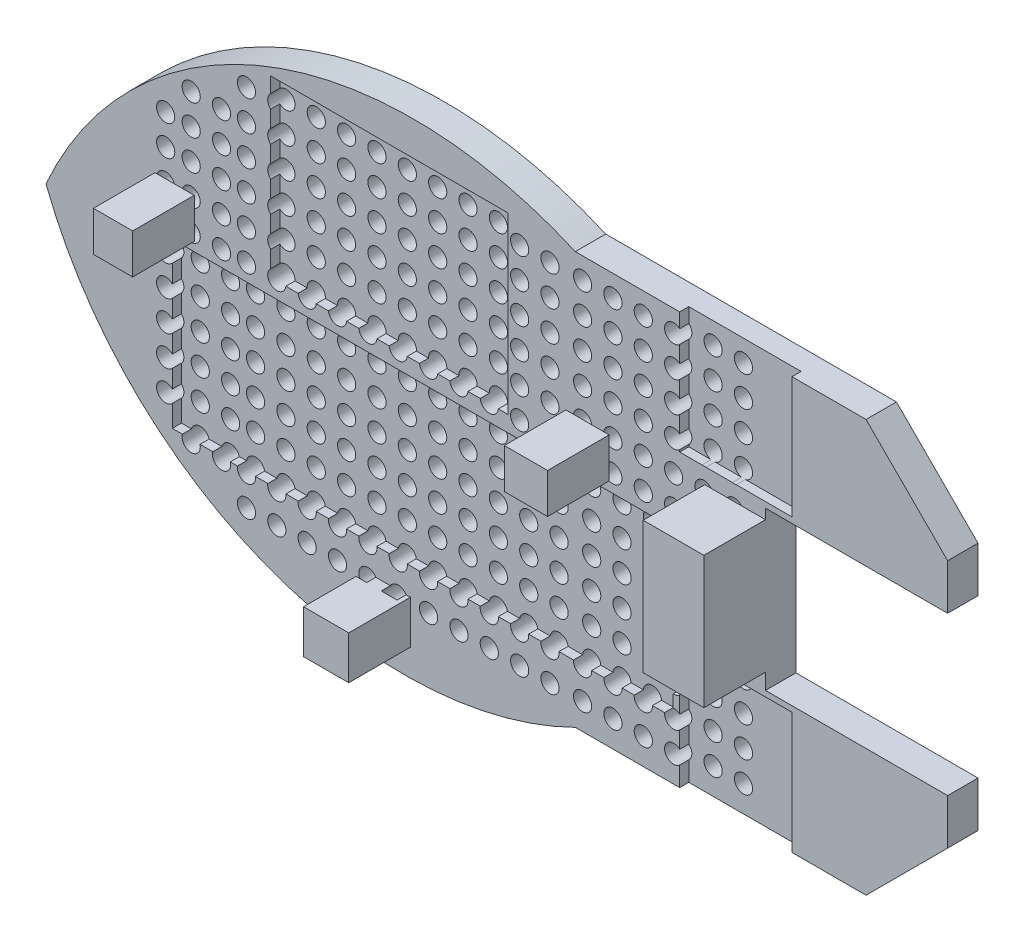
SolidWorks part; units mm, degrees
ref_plane "Front Plane" through (0, 0, 0) normal (0, 0, 1) x (1, 0, 0)
ref_plane "Top Plane" through (0, 0, 0) normal (0, 1, 0) x (1, 0, 0)
ref_plane "Right Plane" through (0, 0, 0) normal (1, 0, 0) x (0, 0, -1)
sketch "Sketch1" plane through (0, 0, 0) normal (0, 0, 1) x (1, 0, 0)
  line L0 (0, 0) -> (0, 26)
  line L1 (0, 0) -> (0, -26)
  line L2 (0, 26) -> (60, 26)
  line L3 (0, -26) -> (60, -26)
  line L4 (60, 26) -> (60, 41)
  line L5 (60, -26) -> (60, -41)
  line L6 (60, 41) -> (33.1299, 67.8701)
  line L7 (33.1299, 67.8701) -> (-62.6465, 67.8701)
  line L8 (60, -41) -> (33.1299, -67.8701)
  line L9 (33.1299, -67.8701) -> (-62.6465, -67.8701)
  line L10 (-62.6465, 67.8701) -> (-62.6465, 83.5456) construction
  line L11 (-62.6465, 83.5456) -> (-62.6465, -86.6983) construction
  arc A3 (-62.6465, 67.8701) -> (-237.0271, 0) centre (-115.9017, -53.2553) ccw
  arc A4 (-237.0271, 0) -> (-62.6465, -67.8701) centre (-118.8598, 45.6551) ccw
  point P15 (-62.6465, -67.8701)
  dimension "D1" = 26
  dimension "D2" = 26
  dimension "D3" = 60
  dimension "D4" = 15
  dimension "D5" = 15
  dimension "D6" = 135
  dimension "D7" = 38
  dimension "D8" = 38
  dimension "D9" = 135
extrude "Boss-Extrude1" add sketch "Sketch1" along normal blind 10 and the other way blind 0.01
sketch "Sketch3" plane through (0, 0, 10) normal (0, 0, 1) x (1, 0, 0)
  line L0 (33.1299, 67.8701) -> (-62.6465, 67.8701) construction
  line L1 (-28.273, 67.8701) -> (8.727, 67.8701)
  line L2 (-28.273, 67.8701) -> (-28.273, 27.8701)
  line L3 (-28.273, 27.8701) -> (8.727, 27.8701)
  line L4 (8.727, 67.8701) -> (8.727, 27.8701)
  dimension "D1" = 40
  dimension "D2" = 37
extrude "Cut-Extrude1" cut sketch "Sketch3" against normal blind 3 contours L2 L1 L4 L3
sketch "Sketch5" plane through (0, 0, 10) normal (0, 0, 1) x (1, 0, 0)
  line L0 (-62.6465, -67.8701) -> (33.1299, -67.8701) construction
  line L1 (-28.273, -27.8701) -> (8.727, -27.8701)
  line L2 (-28.273, -27.8701) -> (-28.273, -67.8701)
  line L3 (-28.273, -67.8701) -> (8.727, -67.8701)
  line L4 (8.727, -27.8701) -> (8.727, -67.8701)
extrude "Cut-Extrude3" cut sketch "Sketch5" against normal blind 3
sketch "Sketch7" plane through (0, 0, 10) normal (0, 0, 1) x (1, 0, 0)
  line L1 (-195.4131, 5.0562) -> (-30.4131, 5.0562)
  line L2 (-195.4131, 5.0562) -> (-195.4131, -48.9438)
  line L3 (-195.4131, -48.9438) -> (-30.4131, -48.9438)
  line L4 (-30.4131, 5.0562) -> (-30.4131, -48.9438)
  dimension "D1" = 54
  dimension "D2" = 165
extrude "Cut-Extrude4" cut sketch "Sketch7" against normal blind 3
sketch "Sketch8" plane through (0, 0, 10) normal (0, 0, 1) x (1, 0, 0)
  line L1 (-162.9927, 67.8133) -> (-84.7927, 67.8133)
  line L2 (-162.9927, 67.8133) -> (-162.9927, 10.3133)
  line L3 (-162.9927, 10.3133) -> (-84.7927, 10.3133)
  line L4 (-84.7927, 67.8133) -> (-84.7927, 10.3133)
  dimension "D1" = 78.2
  dimension "D2" = 57.5
extrude "Cut-Extrude5" cut sketch "Sketch8" against normal blind 3
sketch "Sketch9" plane through (0, 0, 10) normal (0, 0, 1) x (1, 0, 0)
  line L1 (-201.1086, 21.1542) -> (-188.1842, 21.1542)
  line L2 (-201.1086, 21.1542) -> (-201.1086, 8.0108)
  line L3 (-201.1086, 8.0108) -> (-188.1842, 8.0108)
  line L4 (-188.1842, 21.1542) -> (-188.1842, 8.0108)
  line L5 (-65.7317, 21.1542) -> (-51.493, 21.1542)
  line L6 (-65.7317, 21.1542) -> (-65.7317, 8.0108)
  line L7 (-65.7317, 8.0108) -> (-51.493, 8.0108)
  line L8 (-51.493, 21.1542) -> (-51.493, 8.0108)
  line L9 (-131.8867, -57.9252) -> (-116.9909, -57.9252)
  line L10 (-131.8867, -57.9252) -> (-131.8867, -72.1638)
  line L11 (-131.8867, -72.1638) -> (-116.9909, -72.1638)
  line L12 (-116.9909, -57.9252) -> (-116.9909, -72.1638)
extrude "Boss-Extrude2" add sketch "Sketch9" along normal blind 20.3
sketch "Sketch11" plane through (0, 0, -0.01) normal (0, 0, -1) x (-1, 0, 0)
  circle A0 centre (70.989, 60.5844) radius 3
  circle A1 centre (80.989, 60.5844) radius 3
  circle A2 centre (90.989, 60.5844) radius 3
  circle A3 centre (100.989, 60.5844) radius 3
  circle A4 centre (110.989, 60.5844) radius 3
  circle A5 centre (120.989, 60.5844) radius 3
  circle A6 centre (130.989, 60.5844) radius 3
  circle A7 centre (140.989, 60.5844) radius 3
  circle A8 centre (150.989, 60.5844) radius 3
  circle A9 centre (160.989, 60.5844) radius 3
  circle A10 centre (170.989, 60.5844) radius 3
  circle A11 centre (80.989, 50.5844) radius 3
  circle A12 centre (90.989, 50.5844) radius 3
  circle A13 centre (100.989, 50.5844) radius 3
  circle A14 centre (110.989, 50.5844) radius 3
  circle A15 centre (120.989, 50.5844) radius 3
  circle A16 centre (130.989, 50.5844) radius 3
  circle A17 centre (140.989, 50.5844) radius 3
  circle A18 centre (150.989, 50.5844) radius 3
  circle A19 centre (160.989, 50.5844) radius 3
  circle A20 centre (170.989, 50.5844) radius 3
  circle A21 centre (80.989, 40.5844) radius 3
  circle A22 centre (90.989, 40.5844) radius 3
  circle A23 centre (100.989, 40.5844) radius 3
  circle A24 centre (110.989, 40.5844) radius 3
  circle A25 centre (120.989, 40.5844) radius 3
  circle A26 centre (130.989, 40.5844) radius 3
  circle A27 centre (140.989, 40.5844) radius 3
  circle A28 centre (150.989, 40.5844) radius 3
  circle A29 centre (160.989, 40.5844) radius 3
  circle A30 centre (170.989, 40.5844) radius 3
  circle A31 centre (80.989, 30.5844) radius 3
  circle A32 centre (90.989, 30.5844) radius 3
  circle A33 centre (100.989, 30.5844) radius 3
  circle A34 centre (110.989, 30.5844) radius 3
  circle A35 centre (120.989, 30.5844) radius 3
  circle A36 centre (130.989, 30.5844) radius 3
  circle A37 centre (140.989, 30.5844) radius 3
  circle A38 centre (150.989, 30.5844) radius 3
  circle A39 centre (160.989, 30.5844) radius 3
  circle A40 centre (170.989, 30.5844) radius 3
  circle A41 centre (80.989, 20.5844) radius 3
  circle A42 centre (90.989, 20.5844) radius 3
  circle A43 centre (100.989, 20.5844) radius 3
  circle A44 centre (110.989, 20.5844) radius 3
  circle A45 centre (120.989, 20.5844) radius 3
  circle A46 centre (130.989, 20.5844) radius 3
  circle A47 centre (140.989, 20.5844) radius 3
  circle A48 centre (150.989, 20.5844) radius 3
  circle A49 centre (160.989, 20.5844) radius 3
  circle A50 centre (170.989, 20.5844) radius 3
  circle A51 centre (80.989, 10.5844) radius 3
  circle A52 centre (90.989, 10.5844) radius 3
  circle A53 centre (100.989, 10.5844) radius 3
  circle A54 centre (110.989, 10.5844) radius 3
  circle A55 centre (120.989, 10.5844) radius 3
  circle A56 centre (130.989, 10.5844) radius 3
  circle A57 centre (140.989, 10.5844) radius 3
  circle A58 centre (150.989, 10.5844) radius 3
  circle A59 centre (160.989, 10.5844) radius 3
  circle A60 centre (170.989, 10.5844) radius 3
  circle A61 centre (80.989, 0.5844) radius 3
  circle A62 centre (90.989, 0.5844) radius 3
  circle A63 centre (100.989, 0.5844) radius 3
  circle A64 centre (110.989, 0.5844) radius 3
  circle A65 centre (120.989, 0.5844) radius 3
  circle A66 centre (130.989, 0.5844) radius 3
  circle A67 centre (140.989, 0.5844) radius 3
  circle A68 centre (150.989, 0.5844) radius 3
  circle A69 centre (160.989, 0.5844) radius 3
  circle A70 centre (170.989, 0.5844) radius 3
  circle A71 centre (80.989, -9.4156) radius 3
  circle A72 centre (90.989, -9.4156) radius 3
  circle A73 centre (100.989, -9.4156) radius 3
  circle A74 centre (110.989, -9.4156) radius 3
  circle A75 centre (120.989, -9.4156) radius 3
  circle A76 centre (130.989, -9.4156) radius 3
  circle A77 centre (140.989, -9.4156) radius 3
  circle A78 centre (150.989, -9.4156) radius 3
  circle A79 centre (160.989, -9.4156) radius 3
  circle A80 centre (170.989, -9.4156) radius 3
  circle A81 centre (80.989, -19.4156) radius 3
  circle A82 centre (90.989, -19.4156) radius 3
  circle A83 centre (100.989, -19.4156) radius 3
  circle A84 centre (110.989, -19.4156) radius 3
  circle A85 centre (120.989, -19.4156) radius 3
  circle A86 centre (130.989, -19.4156) radius 3
  circle A87 centre (140.989, -19.4156) radius 3
  circle A88 centre (150.989, -19.4156) radius 3
  circle A89 centre (160.989, -19.4156) radius 3
  circle A90 centre (170.989, -19.4156) radius 3
  circle A91 centre (80.989, -29.4156) radius 3
  circle A92 centre (90.989, -29.4156) radius 3
  circle A93 centre (100.989, -29.4156) radius 3
  circle A94 centre (110.989, -29.4156) radius 3
  circle A95 centre (120.989, -29.4156) radius 3
  circle A96 centre (130.989, -29.4156) radius 3
  circle A97 centre (140.989, -29.4156) radius 3
  circle A98 centre (150.989, -29.4156) radius 3
  circle A99 centre (160.989, -29.4156) radius 3
  circle A100 centre (170.989, -29.4156) radius 3
  circle A101 centre (80.989, -39.4156) radius 3
  circle A102 centre (90.989, -39.4156) radius 3
  circle A103 centre (100.989, -39.4156) radius 3
  circle A104 centre (110.989, -39.4156) radius 3
  circle A105 centre (120.989, -39.4156) radius 3
  circle A106 centre (130.989, -39.4156) radius 3
  circle A107 centre (140.989, -39.4156) radius 3
  circle A108 centre (150.989, -39.4156) radius 3
  circle A109 centre (160.989, -39.4156) radius 3
  circle A110 centre (170.989, -39.4156) radius 3
  circle A111 centre (80.989, -49.4156) radius 3
  circle A112 centre (90.989, -49.4156) radius 3
  circle A113 centre (100.989, -49.4156) radius 3
  circle A114 centre (110.989, -49.4156) radius 3
  circle A115 centre (120.989, -49.4156) radius 3
  circle A116 centre (130.989, -49.4156) radius 3
  circle A117 centre (140.989, -49.4156) radius 3
  circle A118 centre (150.989, -49.4156) radius 3
  circle A119 centre (160.989, -49.4156) radius 3
  circle A120 centre (170.989, -49.4156) radius 3
  circle A121 centre (80.989, -59.4156) radius 3
  circle A122 centre (90.989, -59.4156) radius 3
  circle A123 centre (100.989, -59.4156) radius 3
  circle A124 centre (110.989, -59.4156) radius 3
  circle A125 centre (120.989, -59.4156) radius 3
  circle A126 centre (130.989, -59.4156) radius 3
  circle A127 centre (140.989, -59.4156) radius 3
  circle A128 centre (150.989, -59.4156) radius 3
  circle A129 centre (160.989, -59.4156) radius 3
  circle A130 centre (170.989, -59.4156) radius 3
  circle A131 centre (70.989, 50.5844) radius 3
  circle A132 centre (70.989, 40.5844) radius 3
  circle A133 centre (70.989, 30.5844) radius 3
  circle A134 centre (70.989, 20.5844) radius 3
  circle A135 centre (70.989, 10.5844) radius 3
  circle A136 centre (70.989, 0.5844) radius 3
  circle A137 centre (70.989, -9.4156) radius 3
  circle A138 centre (70.989, -19.4156) radius 3
  circle A139 centre (70.989, -29.4156) radius 3
  circle A140 centre (70.989, -39.4156) radius 3
  circle A141 centre (70.989, -49.4156) radius 3
  circle A142 centre (70.989, -59.4156) radius 3
  dimension "D1" = 11
  dimension "D2" = 13
extrude "Cut-Extrude12" cut sketch "Sketch11" against normal blind 13
sketch "Sketch12" plane through (0, 0, -0.01) normal (0, 0, -1) x (-1, 0, 0)
  circle A0 centre (179.2029, 50.2603) radius 3
  circle A1 centre (189.2029, 50.2603) radius 3
  circle A2 centre (189.2029, 40.2603) radius 3
  circle A3 centre (189.2029, 30.2603) radius 3
  circle A4 centre (189.2029, 20.2603) radius 3
  circle A5 centre (189.2029, 10.2603) radius 3
  circle A6 centre (189.2029, 0.2603) radius 3
  circle A7 centre (189.2029, -9.7397) radius 3
  circle A8 centre (189.2029, -19.7397) radius 3
  circle A9 centre (189.2029, -29.7397) radius 3
  circle A10 centre (189.2029, -39.7397) radius 3
  circle A11 centre (189.2029, -49.7397) radius 3
  circle A12 centre (179.2029, 40.2603) radius 3
  circle A13 centre (179.2029, 30.2603) radius 3
  circle A14 centre (179.2029, 20.2603) radius 3
  circle A15 centre (179.2029, 10.2603) radius 3
  circle A16 centre (179.2029, 0.2603) radius 3
  circle A17 centre (179.2029, -9.7397) radius 3
  circle A18 centre (179.2029, -19.7397) radius 3
  circle A19 centre (179.2029, -29.7397) radius 3
  circle A20 centre (179.2029, -39.7397) radius 3
  circle A21 centre (179.2029, -49.7397) radius 3
  dimension "D1" = 2
  dimension "D2" = 11
extrude "Cut-Extrude13" cut sketch "Sketch12" against normal up to surface (10.01 mm away) up to face at (-147.989, -59.4156, 10)
sketch "Sketch13" plane through (0, 0, -0.01) normal (0, 0, -1) x (-1, 0, 0)
  circle A0 centre (197.6037, 40.2121) radius 3
  circle A1 centre (197.6037, 30.2121) radius 3
  circle A2 centre (197.6037, 20.2121) radius 3
  circle A3 centre (197.6037, 10.2121) radius 3
  circle A4 centre (197.6037, 0.2121) radius 3
  circle A5 centre (197.6037, -9.7879) radius 3
  circle A6 centre (197.6037, -19.7879) radius 3
  circle A7 centre (197.6037, -29.7879) radius 3
  circle A8 centre (197.6037, -39.7879) radius 3
  dimension "D1" = 9
extrude "Cut-Extrude14" cut sketch "Sketch13" against normal up to surface (10.01 mm away) up to face at (-176.2029, 40.2603, 10)
sketch "Sketch14" plane through (0, 0, -0.01) normal (0, 0, -1) x (-1, 0, 0)
  circle A0 centre (60.2552, 60.8035) radius 3
  circle A1 centre (50.2552, 60.8035) radius 3
  circle A2 centre (40.2552, 60.8035) radius 3
  circle A3 centre (30.2552, 60.8035) radius 3
  circle A4 centre (20.2552, 60.8035) radius 3
  circle A5 centre (10.2552, 60.8035) radius 3
  circle A6 centre (50.2552, 50.8035) radius 3
  circle A7 centre (40.2552, 50.8035) radius 3
  circle A8 centre (30.2552, 50.8035) radius 3
  circle A9 centre (20.2552, 50.8035) radius 3
  circle A10 centre (10.2552, 50.8035) radius 3
  circle A11 centre (50.2552, 40.8035) radius 3
  circle A12 centre (40.2552, 40.8035) radius 3
  circle A13 centre (30.2552, 40.8035) radius 3
  circle A14 centre (20.2552, 40.8035) radius 3
  circle A15 centre (10.2552, 40.8035) radius 3
  circle A16 centre (50.2552, 30.8035) radius 3
  circle A17 centre (40.2552, 30.8035) radius 3
  circle A18 centre (30.2552, 30.8035) radius 3
  circle A19 centre (20.2552, 30.8035) radius 3
  circle A20 centre (10.2552, 30.8035) radius 3
  circle A21 centre (50.2552, 20.8035) radius 3
  circle A22 centre (40.2552, 20.8035) radius 3
  circle A23 centre (30.2552, 20.8035) radius 3
  circle A24 centre (20.2552, 20.8035) radius 3
  circle A25 centre (10.2552, 20.8035) radius 3
  circle A26 centre (50.2552, 10.8035) radius 3
  circle A27 centre (40.2552, 10.8035) radius 3
  circle A28 centre (30.2552, 10.8035) radius 3
  circle A29 centre (20.2552, 10.8035) radius 3
  circle A30 centre (10.2552, 10.8035) radius 3
  circle A31 centre (50.2552, 0.8035) radius 3
  circle A32 centre (40.2552, 0.8035) radius 3
  circle A33 centre (30.2552, 0.8035) radius 3
  circle A34 centre (20.2552, 0.8035) radius 3
  circle A35 centre (10.2552, 0.8035) radius 3
  circle A36 centre (50.2552, -9.1965) radius 3
  circle A37 centre (40.2552, -9.1965) radius 3
  circle A38 centre (30.2552, -9.1965) radius 3
  circle A39 centre (20.2552, -9.1965) radius 3
  circle A40 centre (10.2552, -9.1965) radius 3
  circle A41 centre (50.2552, -19.1965) radius 3
  circle A42 centre (40.2552, -19.1965) radius 3
  circle A43 centre (30.2552, -19.1965) radius 3
  circle A44 centre (20.2552, -19.1965) radius 3
  circle A45 centre (10.2552, -19.1965) radius 3
  circle A46 centre (50.2552, -29.1965) radius 3
  circle A47 centre (40.2552, -29.1965) radius 3
  circle A48 centre (30.2552, -29.1965) radius 3
  circle A49 centre (20.2552, -29.1965) radius 3
  circle A50 centre (10.2552, -29.1965) radius 3
  circle A51 centre (50.2552, -39.1965) radius 3
  circle A52 centre (40.2552, -39.1965) radius 3
  circle A53 centre (30.2552, -39.1965) radius 3
  circle A54 centre (20.2552, -39.1965) radius 3
  circle A55 centre (10.2552, -39.1965) radius 3
  circle A56 centre (50.2552, -49.1965) radius 3
  circle A57 centre (40.2552, -49.1965) radius 3
  circle A58 centre (30.2552, -49.1965) radius 3
  circle A59 centre (20.2552, -49.1965) radius 3
  circle A60 centre (10.2552, -49.1965) radius 3
  circle A61 centre (50.2552, -59.1965) radius 3
  circle A62 centre (40.2552, -59.1965) radius 3
  circle A63 centre (30.2552, -59.1965) radius 3
  circle A64 centre (20.2552, -59.1965) radius 3
  circle A65 centre (10.2552, -59.1965) radius 3
  circle A66 centre (60.2552, 50.8035) radius 3
  circle A67 centre (60.2552, 40.8035) radius 3
  circle A68 centre (60.2552, 30.8035) radius 3
  circle A69 centre (60.2552, 20.8035) radius 3
  circle A70 centre (60.2552, 10.8035) radius 3
  circle A71 centre (60.2552, 0.8035) radius 3
  circle A72 centre (60.2552, -9.1965) radius 3
  circle A73 centre (60.2552, -19.1965) radius 3
  circle A74 centre (60.2552, -29.1965) radius 3
  circle A75 centre (60.2552, -39.1965) radius 3
  circle A76 centre (60.2552, -49.1965) radius 3
  circle A77 centre (60.2552, -59.1965) radius 3
  dimension "D1" = 6
  dimension "D2" = 13
extrude "Cut-Extrude16" cut sketch "Sketch14" against normal up to surface (10.01 mm away) up to face at (-194.6037, 40.2121, 10)
sketch "Sketch15" plane through (0, 0, 10) normal (0, 0, 1) x (1, 0, 0)
  line L0 (0, -26) -> (0, 26) construction
  line L1 (-20, 22.7016) -> (0, 22.7016)
  line L2 (-20, 22.7016) -> (-20, -20.7984)
  line L3 (-20, -20.7984) -> (0, -20.7984)
  line L4 (0, 22.7016) -> (0, -20.7984)
  dimension "D1" = 43.5
  dimension "D2" = 20
extrude "Boss-Extrude3" add sketch "Sketch15" along normal blind 20.3
sketch "Sketch4" plane through (0, 0, 7) normal (0, 0, 1) x (1, 0, 0)
  line L1 (-28.3661, -27.8728) -> (8.6339, -27.8728)
  line L2 (-28.3661, -27.8728) -> (-28.3661, -67.8728)
  line L3 (-28.3661, -67.8728) -> (8.6339, -67.8728)
  line L4 (8.6339, -27.8728) -> (8.6339, -67.8728)
  dimension "D1" = 40
  dimension "D2" = 37
